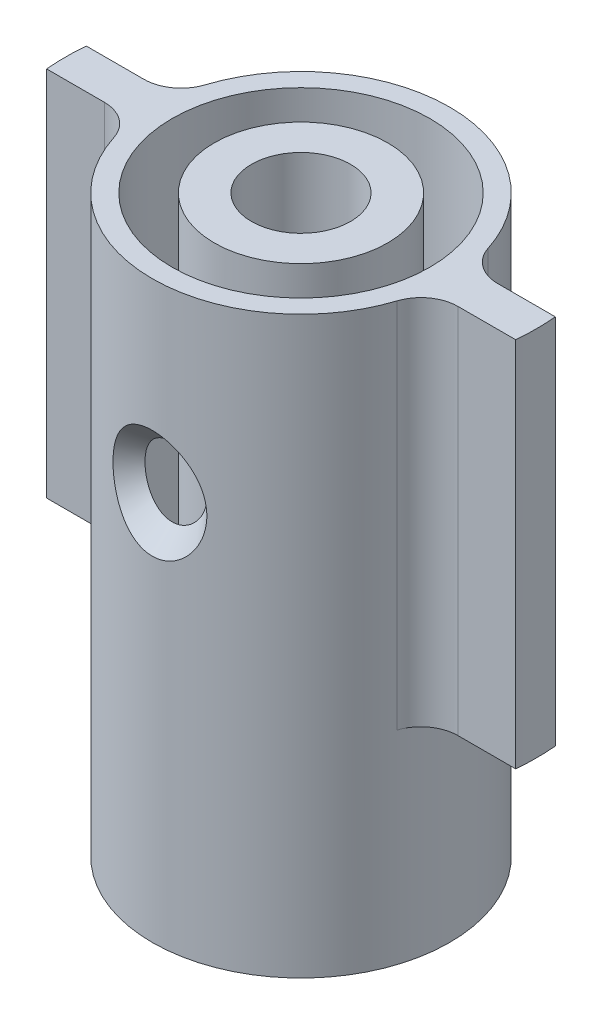
SolidWorks part; units mm, degrees
note: The reader was unsure of these and kept them because the rebuilt part matched: shared geometry of "Sketch1<3>", "Sketch1<4>".
ref_plane "Front Plane" through (0, 0, 0) normal (0, 0, 1) x (1, 0, 0)
ref_plane "Top Plane" through (0, 0, 0) normal (0, 1, 0) x (1, 0, 0)
ref_plane "Right Plane" through (0, 0, 0) normal (1, 0, 0) x (0, 0, -1)
sketch "Sketch1" plane through (0, 0, 0) normal (0, 1, 0) x (1, 0, 0)
  line L1 (3.5, -2.0207) -> (3.5, 2.0207)
  line L2 (3.5, 2.0207) -> (0, 4.0415)
  line L3 (0, 4.0415) -> (-3.5, 2.0207)
  line L4 (-3.5, 2.0207) -> (-3.5, -2.0207)
  line L5 (-3.5, -2.0207) -> (0, -4.0415)
  line L6 (0, -4.0415) -> (3.5, -2.0207)
  circle A0 centre (0, 0) radius 2
  circle A1 centre (0, 0) radius 3.5 construction
  circle A2 centre (0, 0) radius 3.5
  circle A3 centre (0, 0) radius 6
  dimension "D1" = 4
  dimension "D3" = 7
  dimension "D4" = 12
  dimension "D2" = 7
extrude "Boss-Extrude1" add sketch "Sketch1" along normal blind 20 contours A2 A0
extrude "Boss-Extrude2" add sketch "Sketch1<3>" against normal blind 3.2 contours A3 L6 L5 L4 L3 L2 L1
sketch "Sketch1<3>" plane through (0, 0, 0) normal (0, 1, 0) x (1, 0, 0) same geometry as "Sketch1"
extrude "Boss-Extrude3" add sketch "Sketch1<4>" along normal blind 5 contours A2 L3 L4 | A2 L4 L5 | A2 L5 L6 | A2 L6 L1 | A2 L1 L2 | A2 L2 L3 | A3 L6 L5 L4 L3 L2 L1
sketch "Sketch1<4>" plane through (0, 0, 0) normal (0, 1, 0) x (1, 0, 0) same geometry as "Sketch1"
sketch "Sketch2" plane through (0, 5, 0) normal (0, 1, 0) x (1, 0, 0)
  line L0 (-5.9464, 0.8) -> (-9.4663, 0.8)
  line L1 (-9.4663, -0.8) -> (-5.9464, -0.8)
  line L2 (0, 0) -> (0, 9.5) construction
  line L3 (9.4663, -0.8) -> (5.9464, -0.8)
  line L4 (5.9464, 0.8) -> (9.4663, 0.8)
  circle A0 centre (0, 0) radius 5.2
  circle A1 centre (0, 0) radius 9.5
  circle A2 centre (0, 0) radius 6
  dimension "D1" = 10.4
  dimension "D2" = 19
  dimension "D3" = 12
  dimension "D4" = 1.6
extrude "Boss-Extrude4" add sketch "Sketch2" along normal blind 15
ref_plane "Plane1" through (0, 0, -6) normal (0, 0, -1) x (-1, 0, 0)
sketch "Sketch3" plane through (0, 0, -6) normal (0, 0, -1) x (-1, 0, 0)
  line L0 (9.4663, 20) -> (9.4663, 5) construction
  line L1 (-9.4663, 20) -> (-9.4663, 5) construction
  line L2 (9.4663, 20) -> (9.4663, 5) construction
  line L3 (-9.4663, 20) -> (-9.4663, 5) construction
  line L4 (-9.4663, 20) -> (9.4663, 5) construction
  point P4 (0, 12.5)
hole_wizard "CSK for M2 Flat Head Machine Screw1" positions "Sketch3" profile "Sketch5" countersink size "M2" standard "ANSI Metric"
sketch "Sketch5" plane through (0, 12.5, -6) normal (1, 0, 0) x (0, 1, 0)
  line L0 (0, 0) -> (0, 5)
  line L1 (0, 5) -> (1.2, 4.279)
  line L2 (1.2, 4.279) -> (1.2, 1)
  line L3 (1.2, 1) -> (2.2, 0)
  line L5 (2.2, 0) -> (0, 0)
  line L6 (-1.2, 1) -> (-2.2, 0) construction
  line L10 (0, 5) -> (-1.2, 4.279) construction
  line L11 (0, -6.35) -> (0, 107.95) construction
  dimension "Hole Dia." = 2.4
  dimension "Hole Depth" = 5
  dimension "Near C'Sink Dia." = 4.4
  dimension "Near C'Sink Angle" = 90
  dimension "Drill Angle" = 118
pattern_circular "CirPattern1" count 2 over 360 about axis through (0, 5, 0) along (0, -1, 0) of "CSK for M2 Flat Head Machine Screw1"
fillet "Fillet1" radius 1.5 4 edges at (-5.9464, 12.5, 0.8) (5.9464, 12.5, 0.8) (5.9464, 12.5, -0.8) (-5.9464, 12.5, -0.8)
